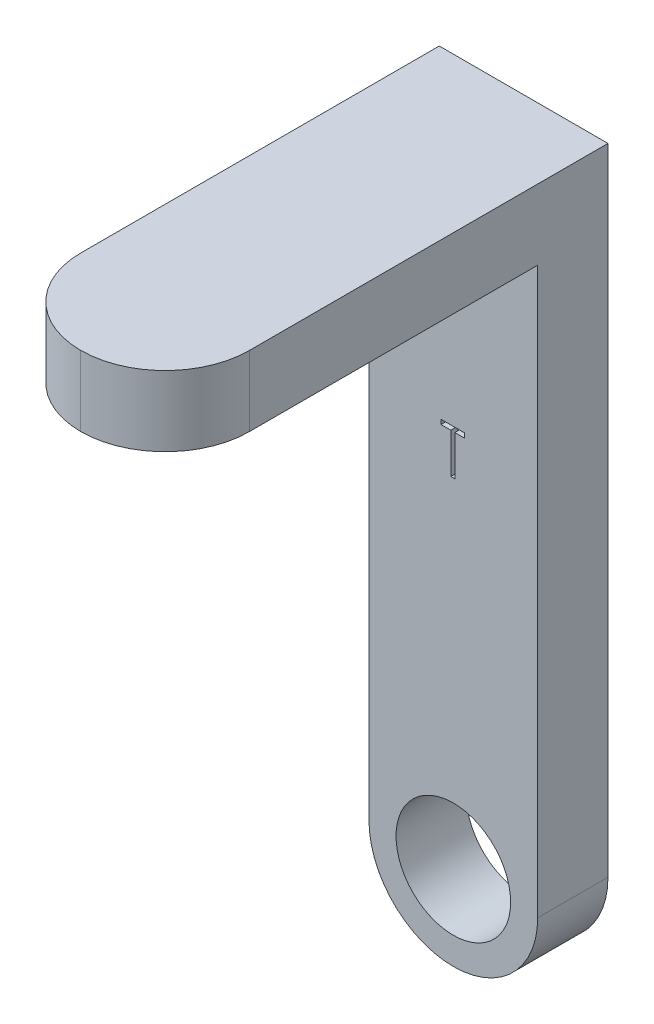
SolidWorks part; units mm, degrees
other "Markup1"
sketch "Sketch5" plane through (-6, -6, 29.23) normal (-0.05, -0.8171, 0.5743) x (0.9987, -0.0424, 0.0267)
ref_plane "Front Plane" through (0, 0, 0) normal (0, 0, 1) x (1, 0, 0)
ref_plane "Top Plane" through (0, 0, 0) normal (0, 1, 0) x (1, 0, 0)
ref_plane "Right Plane" through (0, 0, 0) normal (1, 0, 0) x (0, 0, -1)
sketch "Sketch1" plane through (0, 0, 0) normal (0, 0, 1) x (1, 0, 0)
  line L0 (-2.8373, 2.925) -> (2.8373, 2.925)
  arc A0 (-2.8373, 2.925) -> (2.8373, 2.925) centre (0, 0) ccw
  circle A1 centre (0, 0) radius 6
  point P5 (0, -4.075)
  point P6 (0, 2.925)
  dimension "D1" = 8.15
  dimension "D3" = 12
  dimension "D2" = 7
extrude "Boss-Extrude1" add sketch "Sketch1" along normal blind 5
sketch "Sketch2" plane through (0, 0, 5) normal (0, 0, 1) x (1, 0, 0)
  line L0 (-6, 0) -> (-6, 45.2)
  line L1 (6, 0) -> (6, 45.2)
  line L2 (6, 45.2) -> (-6, 45.2)
  circle A0 centre (0, 0) radius 6 construction
  arc A1 (6, 0) -> (-6, 0) centre (0, 0) ccw
  dimension "D1" = 45.2
extrude "Boss-Extrude2" add sketch "Sketch2" against normal blind 5
sketch "Sketch3" plane through (0, 0, 5) normal (0, 0, 1) x (1, 0, 0)
  circle A0 centre (0, 0) radius 4.075
  dimension "D1" = 8.15
extrude "Cut-Extrude1" cut sketch "Sketch3" against normal blind 3
sketch "Sketch4" plane through (0, 0, 5) normal (0, 0, 1) x (1, 0, 0)
  line L0 (-6, 45.2) -> (-6, 40.2)
  line L1 (-6, 45.2) -> (-6, 0) construction
  line L2 (-6, 40.2) -> (6, 40.2)
  line L3 (6, 0) -> (6, 45.2) construction
  line L4 (6, 40.2) -> (6, 45.2)
  line L5 (6, 45.2) -> (-6, 45.2)
  dimension "D1" = 5
extrude "Boss-Extrude3" add sketch "Sketch4" along normal blind 26.5
fillet "Fillet1" radius 6 2 edges at (-6, 42.7, 31.5) (6, 42.7, 31.5)
sketch "Sketch6" plane through (0, 0, 5) normal (0, 0, 1) x (1, 0, 0)
  line L0 (-0.9136, 24.0947) -> (6, 24.0947) construction
  line L2 (6, 0) -> (6, 40.2) construction
  line L3 (0, 40.2) -> (0, 0) construction
  line L4 (-6, 40.2) -> (6, 40.2) construction
  text T0 "T"
extrude "Cut-Extrude2" cut sketch "Sketch6" against normal blind 0.5
